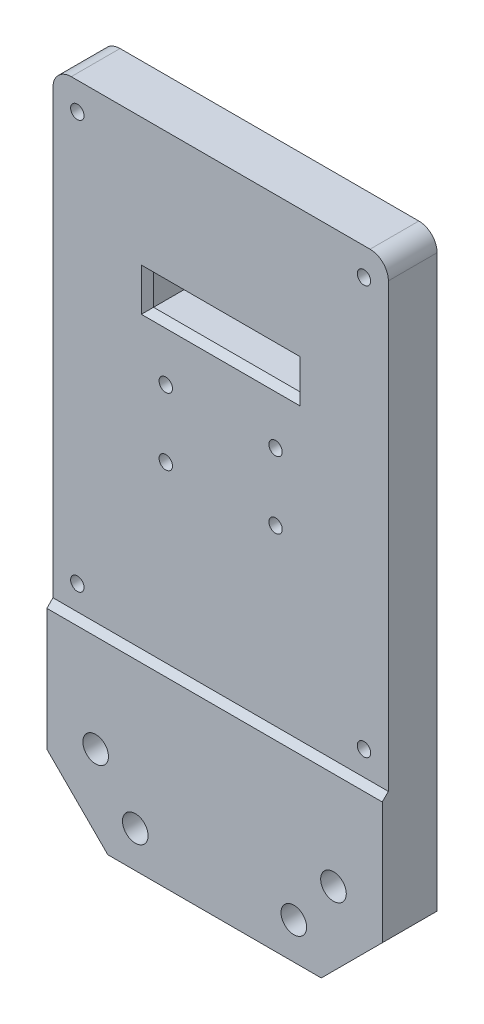
SolidWorks part; units mm, degrees
ref_plane "前视基准面" through (0, 0, 0) normal (0, 0, 1) x (1, 0, 0)
ref_plane "上视基准面" through (0, 0, 0) normal (0, 1, 0) x (1, 0, 0)
ref_plane "右视基准面" through (0, 0, 0) normal (1, 0, 0) x (0, 0, -1)
sketch "草图1" plane through (0, 0, 0) normal (0, 1, 0) x (1, 0, 0)
  line L1 (-48, 10) -> (48, 10)
  line L2 (-48, 10) -> (-48, -10)
  line L3 (-48, -10) -> (48, -10)
  line L4 (48, 10) -> (48, -10)
  line L5 (-48, 10) -> (48, -10) construction
  line L6 (-48, -10) -> (48, 10) construction
  point P0 (0, 0)
  dimension "D1" = 96
extrude "凸台-拉伸1" add sketch "草图1" along normal blind 10 contours L2 L3 L4 L1
sketch "草图4" plane through (0, 10, 0) normal (0, 1, 0) x (1, 0, 0)
  line L0 (-48, 10) -> (48, 10) construction
  line L1 (-29.9845, -10) -> (29.9845, -10)
  line L2 (-29.9845, -10) -> (-29.9845, 10)
  line L3 (-29.9845, 10) -> (29.9845, 10)
  line L4 (29.9845, -10) -> (29.9845, 10)
  line L5 (-29.9845, -10) -> (29.9845, 10) construction
  line L6 (-29.9845, 10) -> (29.9845, -10) construction
  point P0 (0, 0)
extrude "凸台-拉伸2" add sketch "草图4" along normal blind 67
sketch "草图6" plane through (0, 0, 10) normal (0, 0, 1) x (1, 0, 0)
  line L0 (0, 0) -> (0, 77) construction
  line L1 (-30, 35.5) -> (30, 35.5) construction
  line L2 (-29.9845, 77) -> (29.9845, 77) construction
  line L3 (0, 77) -> (0, 35.5) construction
  line L4 (0, 30) -> (0, 4) construction
  line L5 (-2.5, 33.25) -> (2.5, 33.25) construction
  line L6 (-2.5, 33.25) -> (-2.5, 37.75) construction
  line L7 (-2.5, 37.75) -> (2.5, 37.75) construction
  line L8 (2.5, 33.25) -> (2.5, 37.75) construction
  line L9 (-2.5, 33.25) -> (2.5, 37.75) construction
  line L10 (-2.5, 37.75) -> (2.5, 33.25) construction
  line L11 (-9, 41) -> (9, 41) construction
  line L12 (-9, 41) -> (-9, 30) construction
  line L13 (-9, 30) -> (9, 30) construction
  line L14 (9, 41) -> (9, 30) construction
  line L15 (-9, 41) -> (9, 30) construction
  line L16 (-9, 30) -> (9, 41) construction
  line L17 (0, 4) -> (25, 4) construction
  line L18 (25, 4) -> (25, 74) construction
  line L19 (25, 74) -> (-25, 74) construction
  line L20 (-25, 74) -> (-25, 4) construction
  line L21 (-25, 4) -> (0, 4) construction
  line L22 (-25, 4) -> (-23.5, 4) construction
  line L23 (-23.5, 4) -> (-23.5, 5.5) construction
  line L24 (-25, 74) -> (-25, 72.5) construction
  line L25 (-25, 72.5) -> (-23.5, 72.5) construction
  line L26 (-23.5, 72.5) -> (-23.5, 5.5) construction
  line L27 (-23.5, 5.5) -> (23.5, 5.5) construction
  line L28 (23.5, 5.5) -> (23.5, 72.5) construction
  line L29 (23.5, 72.5) -> (-23.5, 72.5) construction
  line L30 (0, 41) -> (0, 55) construction
  line L31 (0, 55) -> (12, 55)
  line L32 (12, 55) -> (12, 50)
  line L33 (12, 50) -> (-12, 50)
  line L34 (-12, 50) -> (-12, 55)
  line L35 (-12, 55) -> (0, 55)
  line L41 (0, 74) -> (0, 4) construction
  line L42 (25, 39) -> (-25, 39) construction
  circle A3 centre (-9, 41) radius 1.1
  circle A4 centre (9, 41) radius 1.1
  circle A5 centre (9, 30) radius 1.1
  circle A6 centre (-9, 30) radius 1.1
  circle A7 centre (-23.5, 72.5) radius 1.1
  circle A8 centre (23.5, 72.5) radius 1.1
  circle A9 centre (23.5, 5.5) radius 1.1
  circle A10 centre (-23.5, 5.5) radius 1.1
  point P126 (0, 39)
  dimension "D1" = 35.5
  dimension "D2" = 70
  dimension "D3" = 1.5
  dimension "D4" = 1.5
  dimension "D5" = 50
extrude "切除-拉伸4" cut sketch "草图6" against normal up to next contours A6 | A5 | A4 | A3
extrude "切除-拉伸5" cut sketch "草图6<8>" against normal blind 11 contours L35 L31 L32 L33 L34
sketch "草图6<8>" plane through (0, 0, 10) normal (0, 0, 1) x (1, 0, 0) same geometry as "草图6"
sketch "草图8" plane through (0, 0, -10) normal (0, 0, -1) x (-1, 0, 0)
  line L1 (-25, 4) -> (25, 4) construction
  line L2 (-25, 4) -> (-25, 74) construction
  line L3 (-25, 74) -> (25, 74) construction
  line L4 (25, 4) -> (25, 74) construction
  line L5 (0, 74) -> (0, 4) construction
  line L6 (-25, 39) -> (25, 39) construction
  line L7 (-29.9845, 1) -> (29.9845, 1)
  line L8 (-29.9845, 1) -> (-29.9845, 77)
  line L9 (-29.9845, 77) -> (29.9845, 77)
  line L10 (29.9845, 1) -> (29.9845, 77)
  line L11 (-29.9845, 1) -> (29.9845, 77) construction
  line L12 (-29.9845, 77) -> (29.9845, 1) construction
  point P4 (0, 39)
  point P148 (0, 39)
extrude "切除-拉伸6" cut sketch "草图8" against normal blind 12
extrude "切除-拉伸7" cut sketch "草图6<9>" against normal up to next contours A10 | A9 | A8 | A7
sketch "草图6<9>" plane through (0, 0, 10) normal (0, 0, 1) x (1, 0, 0) same geometry as "草图6"
sketch "草图9" plane through (0, 0, -10) normal (0, 0, -1) x (-1, 0, 0)
  line L0 (48, 0) -> (-48, 0) construction
  line L1 (-29.9845, 1) -> (29.9983, 1)
  line L2 (-29.9845, 1) -> (-29.9845, 0)
  line L3 (-29.9845, 0) -> (29.9983, 0)
  line L4 (29.9983, 1) -> (29.9983, 0)
  line L5 (0.0069, 0) -> (0.0069, 1) construction
  line L6 (-29.9845, 0.5) -> (29.9983, 0.5) construction
  point P292 (0.0069, 0.5)
extrude "切除-拉伸8" cut sketch "草图9" against normal up to surface (12 mm away) up to face at (-22.4, 72.5, 2)
chamfer "倒角5" distance 1 angle 45 8 edges at (12, 52.5, 10) (0, 50, 10) (0, 55, 10) (-12, 52.5, 10) (12, 52.5, 2) (0, 55, 2) (-12, 52.5, 2) (0, 50, 2)
sketch "草图10" plane through (-48, 0, 0) normal (-1, 0, 0) x (0, 0, 1)
  line L0 (10, 0) -> (-10, 0)
  line L1 (-10, 0) -> (-10, 77)
  line L2 (-10, 77) -> (10, 77)
  line L3 (10, 77) -> (10, 0)
extrude "切除-拉伸9" cut sketch "草图10" against normal blind 20.5
mirror "镜向1" about plane through (0, 0, 0) normal (1, 0, 0) of "切除-拉伸9"
sketch "草图11" plane through (0, 0, 0) normal (0, -1, 0) x (-1, 0, 0)
  line L1 (-27.5, -2) -> (27.5, -2)
  line L2 (-27.5, -2) -> (-27.5, -10)
  line L3 (-27.5, -10) -> (27.5, -10)
  line L4 (27.5, -2) -> (27.5, -10)
  line L5 (0, -10) -> (0, -2) construction
  line L6 (-27.5, -6) -> (27.5, -6) construction
  point P64 (0, -6)
extrude "凸台-拉伸3" add sketch "草图11" along normal up to surface (29.5 mm away)
sketch "草图12" plane through (0, 0, 10) normal (0, 0, 1) x (1, 0, 0)
  line L0 (27.5, -29.5) -> (27.5, 77) construction
  line L1 (-27.5, -29.5) -> (27.5, -29.5)
  line L2 (-27.5, -29.5) -> (-27.5, 0.5)
  line L3 (-27.5, 0.5) -> (27.5, 0.5)
  line L4 (27.5, -29.5) -> (27.5, 0.5)
  line L5 (0, 0.5) -> (0, -29.5) construction
  line L6 (-27.5, -14.5) -> (27.5, -14.5) construction
  point P260 (0, -14.5)
extrude "凸台-拉伸4" add sketch "草图12" along normal blind 1
sketch "草图13" plane through (0, 0, 11) normal (0, 0, 1) x (1, 0, 0)
  circle A0 centre (-19.5, -15.5) radius 2.1
  circle A1 centre (-13, -23.5) radius 2.1
  circle A2 centre (19.5, -15.5) radius 2.1
  circle A3 centre (13, -23.5) radius 2.1
extrude "切除-拉伸10" cut sketch "草图13" against normal up to next
chamfer "倒角6" distance 10 angle 45 2 edges at (27.5, -29.5, 6.5) (-27.5, -29.5, 6.5)
fillet "圆角1" radius 3 2 edges at (27.5, 77, 6) (-27.5, 77, 6)
chamfer "倒角7" distance 1 angle 45 1 edges at (0, 0.5, 10)
